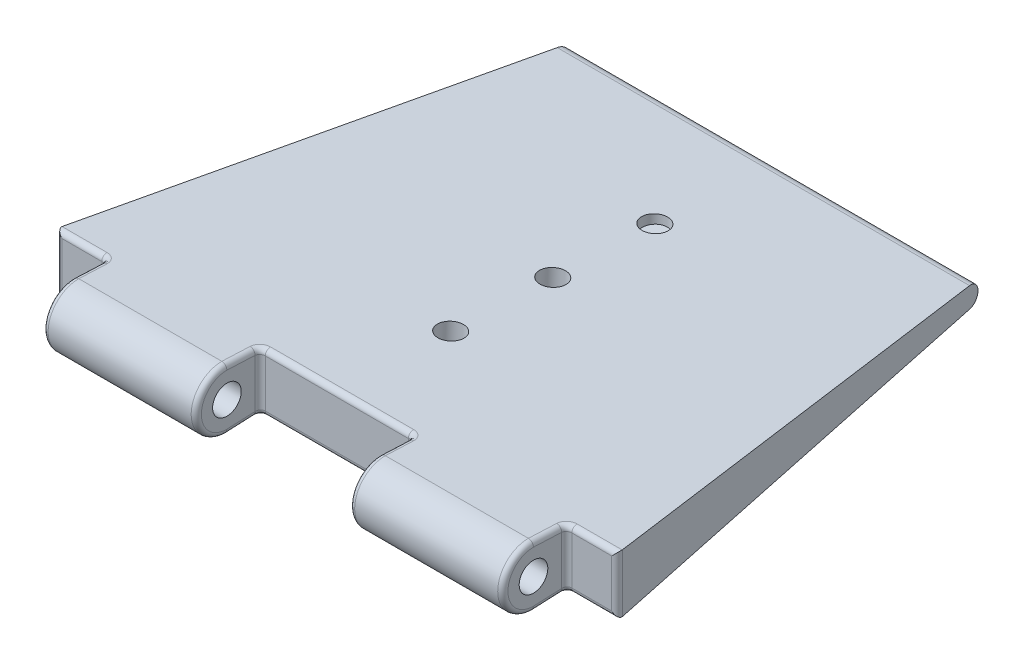
SolidWorks part; units mm, degrees
ref_plane "Front Plane" through (0, 0, 0) normal (0, 0, 1) x (1, 0, 0)
ref_plane "Top Plane" through (0, 0, 0) normal (0, 1, 0) x (1, 0, 0)
ref_plane "Right Plane" through (0, 0, 0) normal (1, 0, 0) x (0, 0, -1)
sketch "Sketch1" plane through (0, 0, 0) normal (1, 0, 0) x (0, 0, -1)
  line L0 (0, 0) -> (45, 0) construction
  line L1 (0, 3) -> (45, 1)
  line L2 (45, -1) -> (0, -3)
  circle A0 centre (0, 0) radius 1.4
  arc A1 (0.2661, 2.9882) -> (0.2661, -2.9882) centre (0, 0) ccw
  arc A2 (45, -1) -> (45, 1) centre (45, 0) ccw
  dimension "D1" = 2.8
  dimension "D2" = 6
  dimension "D3" = 1
  dimension "D4" = 45
extrude "Boss-Extrude1" add sketch "Sketch1" along normal blind 55 contours L2 A2 L1 A1 A0 region at (0, 0, -18.0868)
sketch "Sketch2" plane through (0, 0, 0) normal (0, 1, 0) x (1, 0, 0)
  line L0 (57.5, -3.25) -> (57.5, 3.25) construction
  line L1 (65, -3.25) -> (50, -3.25)
  line L2 (65, -3.25) -> (65, 3.25)
  line L3 (65, 3.25) -> (50, 3.25)
  line L4 (50, -3.25) -> (50, 3.25)
  line L5 (35, -3.25) -> (20, -3.25)
  line L6 (35, -3.25) -> (35, 3.25)
  line L7 (35, 3.25) -> (20, 3.25)
  line L8 (20, -3.25) -> (20, 3.25)
  line L9 (5, -3.25) -> (-10, -3.25)
  line L10 (5, -3.25) -> (5, 3.25)
  line L11 (5, 3.25) -> (-10, 3.25)
  line L12 (-10, -3.25) -> (-10, 3.25)
  line L13 (27.5, -3.25) -> (27.5, 3.25) construction
  line L14 (-2.5, -3.25) -> (-2.5, 3.25) construction
  line L15 (57.5, 0) -> (27.5, 0) construction
  line L16 (27.5, 0) -> (-2.5, 0) construction
  line L17 (55, 0) -> (0, 0) construction
  line L18 (55, -1.4) -> (55, 1.4) construction
  line L19 (55, -1.4) -> (55, 1.4) construction
  point P24 (27.5, 0)
  point P26 (55, 0)
  dimension "D1" = 30
  dimension "D2" = 15
  dimension "D3" = 6.5
extrude "Cut-Extrude1" cut sketch "Sketch2" against normal through all both and the other way through all
sketch "Sketch3" plane through (0, 0, 0) normal (0, 1, 0) x (1, 0, 0)
  line L0 (27.5, -7.7839) -> (27.5, 54.044) construction
  line L1 (5, 3.25) -> (0, 3.25) construction
  line L2 (35, 3.25) -> (20, 3.25) construction
  line L3 (55, 3.25) -> (50, 3.25) construction
  line L4 (5, 3.25) -> (0, 3.25) construction
  line L5 (35, 3.25) -> (20, 3.25) construction
  line L6 (55, 3.25) -> (50, 3.25) construction
  line L7 (55, 3.25) -> (47.5, 46)
  line L8 (47.5, 46) -> (55, 46)
  line L9 (55, 46) -> (55, 3.25)
  line L10 (55, 46) -> (0, 46) construction
  line L11 (7.5, 46) -> (0, 46)
  line L12 (0, 46) -> (0, 3.25)
  line L13 (0, 3.25) -> (7.5, 46)
  point P10 (27.5, 3.25)
  dimension "D1" = 20
extrude "Cut-Extrude2" cut sketch "Sketch3" against normal through all both and the other way through all
fillet "Fillet3" radius 0.5 24 edges at (50, -2.9278, -1.625) (50, 2.9278, -1.625) (5, 2.9278, -1.625) (5, -2.9278, -1.625) (20, -2.9278, -1.625) (20, 2.9278, -1.625) (35, 2.9278, -1.625) (35, -2.9278, -1.625) (50, 0, -3.25) (52.5, 2.8556, -3.25) (55, 0, -3.25) (52.5, -2.8556, -3.25) (0, 0, -3.25) (2.5, 2.8556, -3.25) (5, 0, -3.25) (2.5, -2.8556, -3.25) (20, 0, -3.25) (27.5, 2.8556, -3.25) (35, 0, -3.25) (27.5, -2.8556, -3.25) (5, 0, 3) (20, 0, 3) (35, 0, 3) (50, 0, 3)
sketch "Sketch5" plane through (0, 2.9941, -0.1331) normal (0, 0.999, -0.0444) x (1, 0, 0)
  line L0 (27.5, 3.6427) -> (27.5, 44.9112) construction
  line L1 (20.5, 3.6427) -> (34.5, 3.6427) construction
  line L2 (47.6754, 44.9112) -> (7.3246, 44.9112) construction
  circle A0 centre (27.5, 24.277) radius 1.25
  circle A1 centre (27.5, 14.277) radius 1.25
  circle A2 centre (27.5, 34.277) radius 1.25
  dimension "D3" = 2.5
  dimension "D1" = 10
  dimension "D2" = 10
extrude "Cut-Extrude3" cut sketch "Sketch5" against normal offset from surface (1.9471 mm away) 2 up to face at (27.5, -2.6735, -7.3457)
